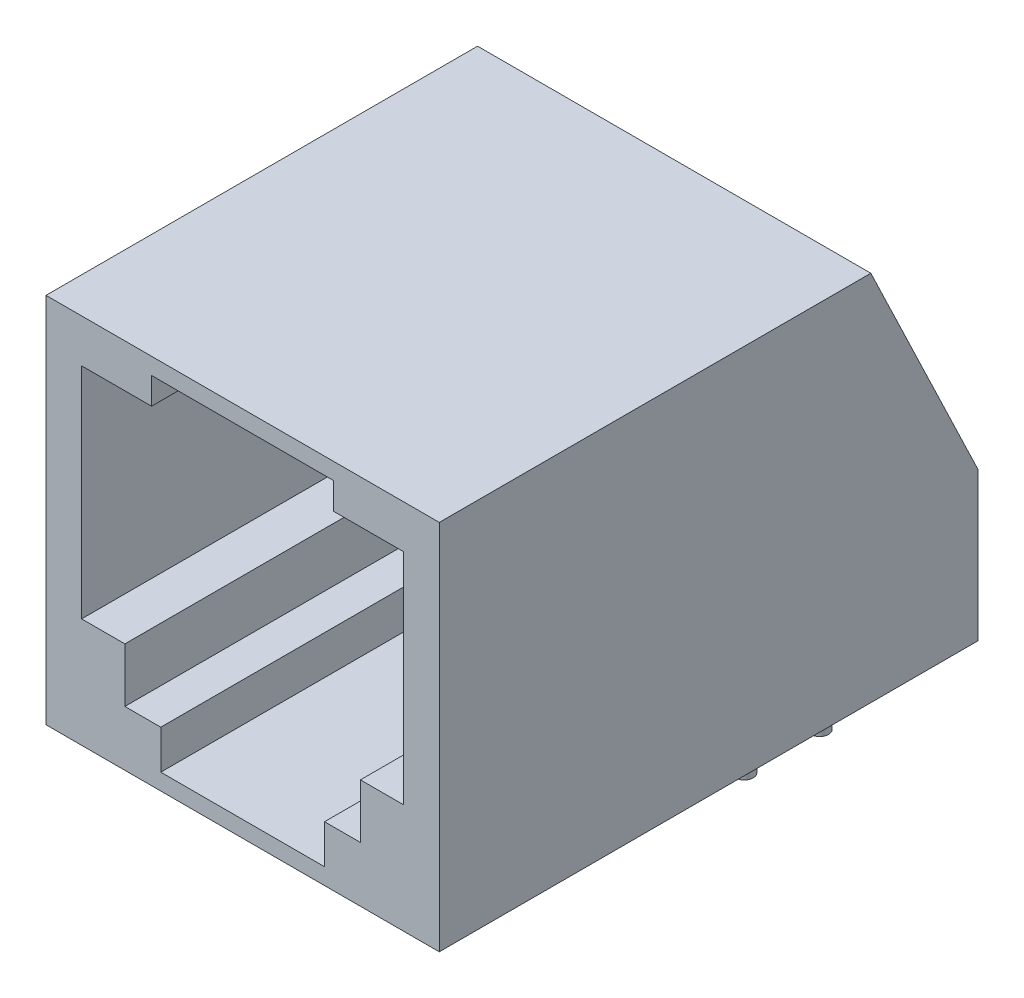
SolidWorks part; units mm, degrees
ref_plane "Front Plane" through (0, 0, 0) normal (0, 0, 1) x (1, 0, 0)
ref_plane "Top Plane" through (0, 0, 0) normal (0, 1, 0) x (1, 0, 0)
ref_plane "Right Plane" through (0, 0, 0) normal (1, 0, 0) x (0, 0, -1)
sketch "Sketch1" plane through (0, 0, 0) normal (1, 0, 0) x (0, 0, -1)
  line L0 (0, 0) -> (0, 12.53)
  line L1 (0, 12.53) -> (14.54, 12.53)
  line L2 (14.54, 12.53) -> (18.15, 5)
  line L3 (18.15, 5) -> (18.15, 0)
  line L4 (18.15, 0) -> (0, 0)
  dimension "D1" = 18.15
  dimension "D2" = 12.53
  dimension "D3" = 5
  dimension "D4" = 14.54
extrude "Boss-Extrude1" add sketch "Sketch1" along normal mid plane 13.25 contours L1 L2 L3 L4 L0
sketch "Sketch2" plane through (0, 0, 0) normal (0, 0, 1) x (1, 0, 0)
  line L0 (-2.7584, 1.8633) -> (-2.7584, 0.55)
  line L1 (-3.9677, 1.8633) -> (-2.7584, 1.8633)
  line L2 (-3.0693, 11.97) -> (3.0693, 11.97)
  line L3 (3.0693, 11.97) -> (3.0693, 11.0732)
  line L4 (3.0693, 11.0732) -> (5.425, 11.0732)
  line L5 (5.425, 11.0732) -> (5.425, 3.6892)
  line L6 (5.425, 3.6892) -> (3.9677, 3.6892)
  line L7 (3.9677, 3.6892) -> (3.9677, 1.8633)
  line L8 (3.9677, 1.8633) -> (2.7584, 1.8633)
  line L9 (2.7584, 1.8633) -> (2.7584, 0.55)
  line L10 (2.7584, 0.55) -> (-2.7584, 0.55)
  line L11 (0, 0) -> (0, 14.1337) construction
  line L12 (-3.9677, 3.6892) -> (-3.9677, 1.8633)
  line L13 (-5.425, 3.6892) -> (-3.9677, 3.6892)
  line L14 (-5.425, 11.0732) -> (-5.425, 3.6892)
  line L15 (-3.0693, 11.0732) -> (-5.425, 11.0732)
  line L16 (-3.0693, 11.97) -> (-3.0693, 11.0732)
  line L17 (6.625, 12.53) -> (-6.625, 12.53) construction
  line L18 (6.625, 0) -> (6.625, 12.53) construction
  line L19 (6.625, 0) -> (-6.625, 0) construction
  point P15 (0, 0.55)
  point P22 (0, 11.97)
  dimension "D1" = 0.56
  dimension "D2" = 1.2
  dimension "D3" = 0.55
extrude "Cut-Extrude1" cut sketch "Sketch2" against normal blind 13.25 contours L15 L14 L13 L12 L1 L0 L10 L9 L8 L7 L6 L5 L4 L3 L2 L16
sketch "Sketch3" plane through (0, 0, 0) normal (0, -1, 0) x (1, 0, 0)
  line L0 (6.625, -18.15) -> (-6.625, -18.15) construction
  line L1 (2.54, -16.9) -> (6.625, -16.9) construction
  line L2 (6.625, -18.15) -> (6.625, 0) construction
  line L3 (-2.54, -16.9) -> (-6.625, -16.9) construction
  line L4 (-6.625, -18.15) -> (-6.625, 0) construction
  line L5 (-2.54, -16.9) -> (-2.54, -14.36) construction
  circle A0 centre (2.54, -16.9) radius 0.3
  circle A1 centre (0, -16.9) radius 0.3
  circle A2 centre (-2.54, -16.9) radius 0.3
  circle A3 centre (0, -14.36) radius 0.3
  circle A4 centre (-2.54, -14.36) radius 0.3
  circle A5 centre (2.54, -14.36) radius 0.3
  dimension "D4" = 0.6
  dimension "D3" = 1.25
  dimension "D5" = 2.54
  dimension "D6" = 2.54
  dimension "D1" = 3
  dimension "D2" = 2
extrude "Boss-Extrude2" add sketch "Sketch3" along normal blind 4
